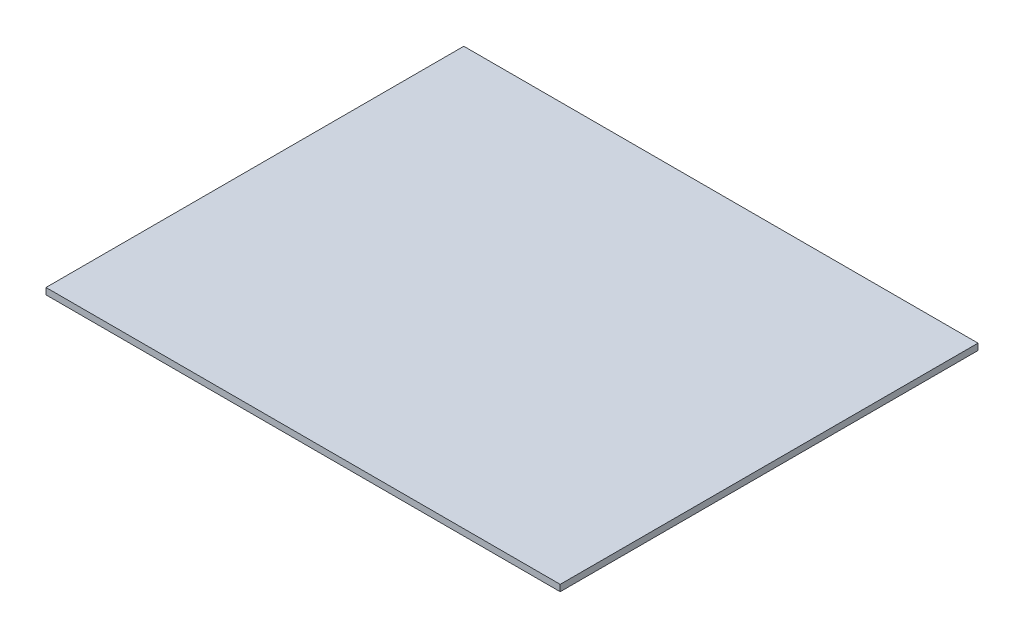
SolidWorks part; units mm, degrees
ref_plane "Front Plane" through (0, 0, 0) normal (0, 0, 1) x (1, 0, 0)
ref_plane "Top Plane" through (0, 0, 0) normal (0, 1, 0) x (1, 0, 0)
ref_plane "Right Plane" through (0, 0, 0) normal (1, 0, 0) x (0, 0, -1)
sketch "Sketch1" plane through (0, 0, 0) normal (0, 1, 0) x (1, 0, 0)
  line L0 (-65, -50) -> (-65, 50)
  line L1 (-63, -48) -> (63, -48)
  line L2 (-63, -48) -> (-63, 10)
  line L4 (63, -48) -> (63, 10)
  line L5 (-65, 50) -> (65, 50)
  line L6 (65, -50) -> (65, 50)
  line L7 (-65, -50) -> (65, -50)
  line L8 (-63, 10) -> (63, 10)
  line L9 (0, 0) -> (0, 10) construction
  line L10 (-63, -48) -> (-63, 48) construction
  line L11 (-63, 48) -> (63, 48) construction
  line L12 (63, -48) -> (63, 48) construction
  line L13 (-80, -65) -> (-80, 65)
  line L14 (-80, 65) -> (80, 65)
  line L15 (80, -65) -> (80, 65)
  line L16 (-80, -65) -> (80, -65)
  point P0 (0, 0)
  point P6 (0, -50)
  point P7 (65, 0)
  point P14 (0, 10)
  dimension "D1" = 100
  dimension "D2" = 130
  dimension "D4" = 40
  dimension "D3" = 2
  dimension "D5" = 15
extrude "Main" add sketch "Sketch1" along normal blind 10 contours L0 L7 L6 L5 L4 L1 L2 region at (0, 0, -24.3942)
ref_plane "BacklitPlane" through (0, 10, 0) normal (0, 1, 0) x (1, 0, 0)
extrude "Boss-Extrude3" add sketch "Sketch1<4>" along normal blind 2 from surface contours L13 L16 L15 L14 L7 L0 L5 L6 | L8 L2 L1 L4 | L0 L7 L6 L5 L2 L8 L4 L1 region at (0, 0, -24.3942) region at (0, 0, 19) region at (-77.9384, 0, 0) starting at plane "BacklitPlane"
sketch "Sketch1<4>" plane through (0, 0, 0) normal (0, 1, 0) x (1, 0, 0) same geometry as "Sketch1"
sketch "Sketch5" plane through (0, 0, 0) normal (0, -1, 0) x (1, 0, 0)
  circle A0 centre (-50, -35) radius 3.5
  dimension "D3" = 7
  dimension "D1" = 50
  dimension "D2" = 35
extrude "Boss-Extrude4" add sketch "Sketch5" along normal blind 4.2
sketch3d "3DSketch2"
  line L0 (-50, -4.2, -35) -> (-50, 0, -35) construction
  point P0 (-50, -4.2, -35)
ref_plane "Plane2" through (0, 0, -35) normal (0, 0, 1) x (1, 0, 0)
sketch "Sketch8" plane through (0, 0, -35) normal (0, 0, 1) x (1, 0, 0)
  line L0 (-50, -8.4) -> (-50, 0) construction
  line L1 (-53.5, 0) -> (-46.5, 0) construction
  line L2 (-43, -4.2) -> (-57, -4.2)
  arc A1 (-57, -4.2) -> (-43, -4.2) centre (-50, 2.9414) ccw
  point P7 (-50, -4.2)
  point P12 (-50, -4.2)
  dimension "D2" = 10
  dimension "D1" = 14
revolve "Revolve1" add sketch "Sketch8" angle 360 about L0 region at (-50, -5.3587, -35)
mirror "Mirror1" about plane through (0, 0, 0) normal (1, 0, 0) of "Revolve1", "Boss-Extrude4"
sketch "Sketch11" plane through (0, 0, 0) normal (0, -1, 0) x (1, 0, 0)
  line L0 (-65, 50) -> (-65, -50) construction
  line L1 (-63, 48) -> (-65, 48)
  line L2 (-63, 48) -> (-63, 42)
  line L3 (-63, 42) -> (-65, 42)
  line L4 (-65, 48) -> (-65, 42)
  line L5 (65, 50) -> (65, -50) construction
  line L6 (63, 48) -> (65, 48)
  line L7 (63, 48) -> (63, 42)
  line L8 (63, 42) -> (65, 42)
  line L9 (65, 48) -> (65, 42)
  line L10 (-63, 48) -> (63, 48) construction
  line L11 (-3, 48) -> (3, 48)
  line L12 (-3, 48) -> (-3, 50)
  line L13 (-3, 50) -> (3, 50)
  line L14 (3, 48) -> (3, 50)
  line L15 (-65, 50) -> (65, 50) construction
  point P22 (0, 48)
  point P23 (0, 48)
  dimension "D1" = 6
  dimension "D2" = 6
  dimension "D3" = 6
extrude "Cut-Extrude1" cut sketch "Sketch11" against normal up to surface (10 mm away) up to face at (0, 10, 0)
